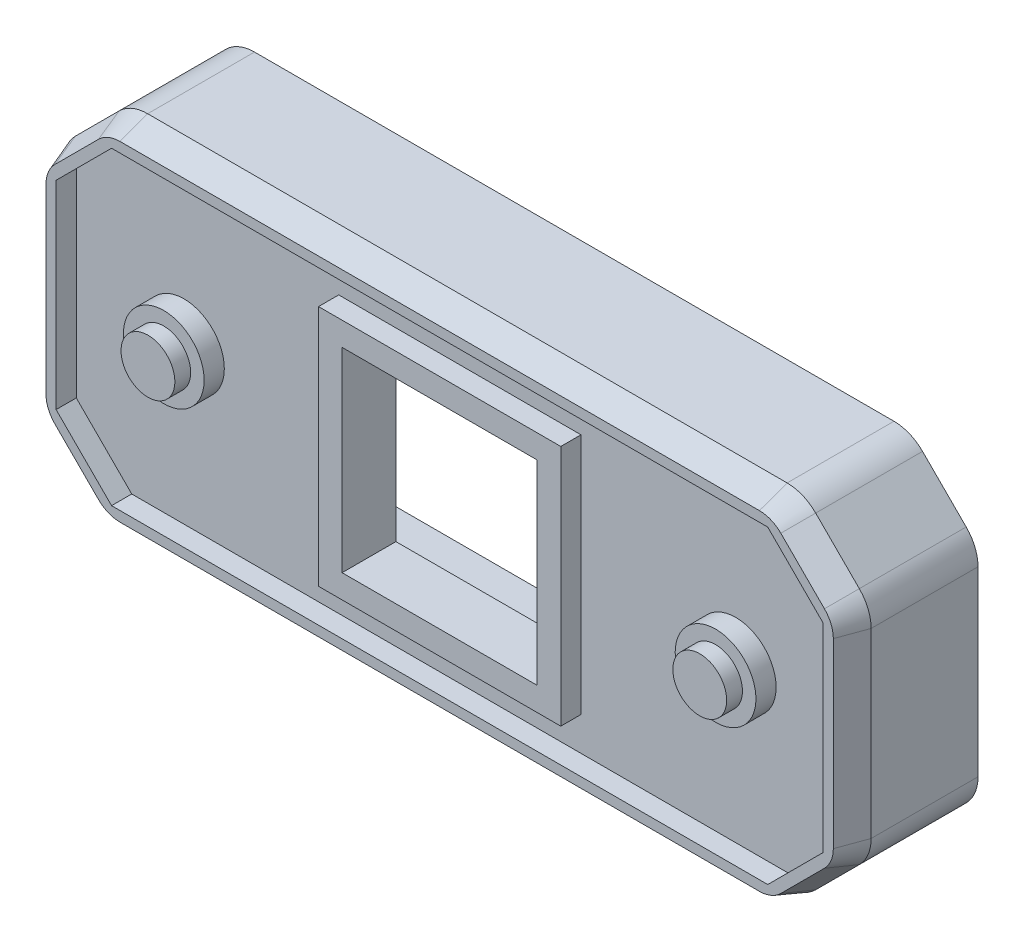
SolidWorks part; units mm, degrees
ref_plane "Front Plane" through (0, 0, 0) normal (0, 0, 1) x (1, 0, 0)
ref_plane "Top Plane" through (0, 0, 0) normal (0, 1, 0) x (1, 0, 0)
ref_plane "Right Plane" through (0, 0, 0) normal (1, 0, 0) x (0, 0, -1)
sketch "Sketch1" plane through (0, 0, 0) normal (0, 0, 1) x (1, 0, 0)
  line L0 (-30, 13) -> (-30, -13)
  line L1 (28, 11) -> (-28, 11)
  line L2 (28, 11) -> (28, -11)
  line L3 (28, -11) -> (-28, -11)
  line L4 (-28, 11) -> (-28, -11)
  line L5 (28, 11) -> (-28, -11) construction
  line L6 (28, -11) -> (-28, 11) construction
  line L7 (30, -13) -> (-30, -13)
  line L8 (30, 13) -> (30, -13)
  line L9 (30, 13) -> (-30, 13)
  point P0 (0, 0)
  dimension "D1" = 22
  dimension "D2" = 56
  dimension "D3" = 2
extrude "Boss-Extrude2" add sketch "Sketch1" along normal blind 10 contours L8 L7 L0 L9
extrude "Cut-Extrude1" cut sketch "Sketch1<5>" along normal blind 6 contours L1 L4 L3 L2 region at (0, 0, 0)
sketch "Sketch1<5>" plane through (0, 0, 0) normal (0, 0, 1) x (1, 0, 0) same geometry as "Sketch1"
chamfer "Chamfer1" distance 5 angle 45 4 edges at (-28, -11, 3) (-28, 11, 3) (28, 11, 3) (28, -11, 3)
sketch "Sketch2" plane through (0, 0, 6) normal (0, 0, -1) x (-1, 0, 0)
  line L1 (7.25, 7.25) -> (-7.25, 7.25)
  line L2 (7.25, 7.25) -> (7.25, -7.25)
  line L3 (7.25, -7.25) -> (-7.25, -7.25)
  line L4 (-7.25, 7.25) -> (-7.25, -7.25)
  line L5 (7.25, 7.25) -> (-7.25, -7.25) construction
  line L6 (7.25, -7.25) -> (-7.25, 7.25) construction
  point P0 (0, 0)
  dimension "D1" = 14.5
extrude "Cut-Extrude2" cut sketch "Sketch2" against normal through all
chamfer "Chamfer2" distance 5 angle 45 4 edges at (-30, -13, 5) (30, -13, 5) (30, 13, 5) (-30, 13, 5)
sketch "Sketch3" plane through (0, 0, 10) normal (0, 0, 1) x (1, 0, 0)
  line L10 (9, 9) -> (-9, 9)
  line L11 (9, 9) -> (9, -9)
  line L12 (9, -9) -> (-9, -9)
  line L13 (-9, 9) -> (-9, -9)
  line L14 (9, 9) -> (-9, -9) construction
  line L15 (9, -9) -> (-9, 9) construction
  line L16 (-28.5, 7.3787) -> (-28.5, -7.3787)
  line L17 (-28.5, -7.3787) -> (-24.3787, -11.5)
  line L18 (-24.3787, -11.5) -> (24.3787, -11.5)
  line L19 (24.3787, -11.5) -> (28.5, -7.3787)
  line L20 (28.5, -7.3787) -> (28.5, 7.3787)
  line L21 (28.5, 7.3787) -> (24.3787, 11.5)
  line L22 (24.3787, 11.5) -> (-24.3787, 11.5)
  line L23 (-24.3787, 11.5) -> (-28.5, 7.3787)
  line L24 (-28.5, 7.3787) -> (-28.5, -7.3787)
  line L25 (-28.5, -7.3787) -> (-24.3787, -11.5)
  line L26 (-24.3787, -11.5) -> (24.3787, -11.5)
  line L27 (24.3787, -11.5) -> (28.5, -7.3787)
  line L28 (28.5, -7.3787) -> (28.5, 7.3787)
  line L29 (28.5, 7.3787) -> (24.3787, 11.5)
  line L30 (24.3787, 11.5) -> (-24.3787, 11.5)
  line L31 (-24.3787, 11.5) -> (-28.5, 7.3787)
  point P2 (0, 0)
  dimension "D2" = 2.5
  dimension "D1" = 1.5
extrude "Cut-Extrude3" cut sketch "Sketch3" against normal blind 1.5
sketch "Sketch4" plane through (0, 0, 8.5) normal (0, 0, 1) x (1, 0, 0)
  line L0 (-28.5, 0) -> (-20.5, 0) construction
  line L1 (-28.5, 7.3787) -> (-28.5, -7.3787) construction
  circle A0 centre (-20.5, 0) radius 3
  dimension "D2" = 6
  dimension "D1" = 8
extrude "Boss-Extrude4" add sketch "Sketch4" along normal blind 1.5
sketch "Sketch5" plane through (0, 0, 10) normal (0, 0, 1) x (1, 0, 0)
  circle A0 centre (-20.5, 0) radius 2
  dimension "D1" = 4
extrude "Boss-Extrude5" add sketch "Sketch5" along normal blind 1.175
mirror "Mirror1" about plane through (0, 0, 0) normal (1, 0, 0) of "Boss-Extrude5", "Boss-Extrude4"
sketch "Sketch6" plane through (0, 0, 6) normal (0, 0, -1) x (-1, 0, 0)
  circle A0 centre (-18.8914, -8.28) radius 1.5
  circle A1 centre (-18.8914, -8.28) radius 0.875
  circle A2 centre (-18.8914, -8.28) radius 0.875
  circle A3 centre (20.9728, 8.32) radius 0.875
  circle A4 centre (20.9728, 8.32) radius 0.875
  circle A5 centre (20.9728, 8.32) radius 1.5
  dimension "D2" = 3
  dimension "D1" = 0
  dimension "D3" = 0
extrude "Boss-Extrude6" add sketch "Sketch6" along normal blind 4.5
chamfer "Chamfer3" distance 2 angle 45 2 edges at (20.3914, -8.28, 6) (-19.4728, 8.32, 6)
fillet "Fillet1" radius 3 8 edges at (30, 8, 5) (25, 13, 5) (-25, 13, 5) (-30, 8, 5) (-30, -8, 5) (-25, -13, 5) (25, -13, 5) (30, -8, 5)
chamfer "Chamfer4" distance 0.75 angle 70 16 edges at (24.9054, 12.7716, 10) (0, 13, 10) (-24.9054, 12.7716, 10) (-27.5, 10.5, 10) (-29.7716, 7.9054, 10) (-30, 0, 10) (-29.7716, -7.9054, 10) (-27.5, -10.5, 10) (-24.9054, -12.7716, 10) (27.5, 10.5, 10) (29.7716, 7.9054, 10) (30, 0, 10) (29.7716, -7.9054, 10) (27.5, -10.5, 10) (24.9054, -12.7716, 10) (0, -13, 10) first distance on face at (0, 0, 10)
